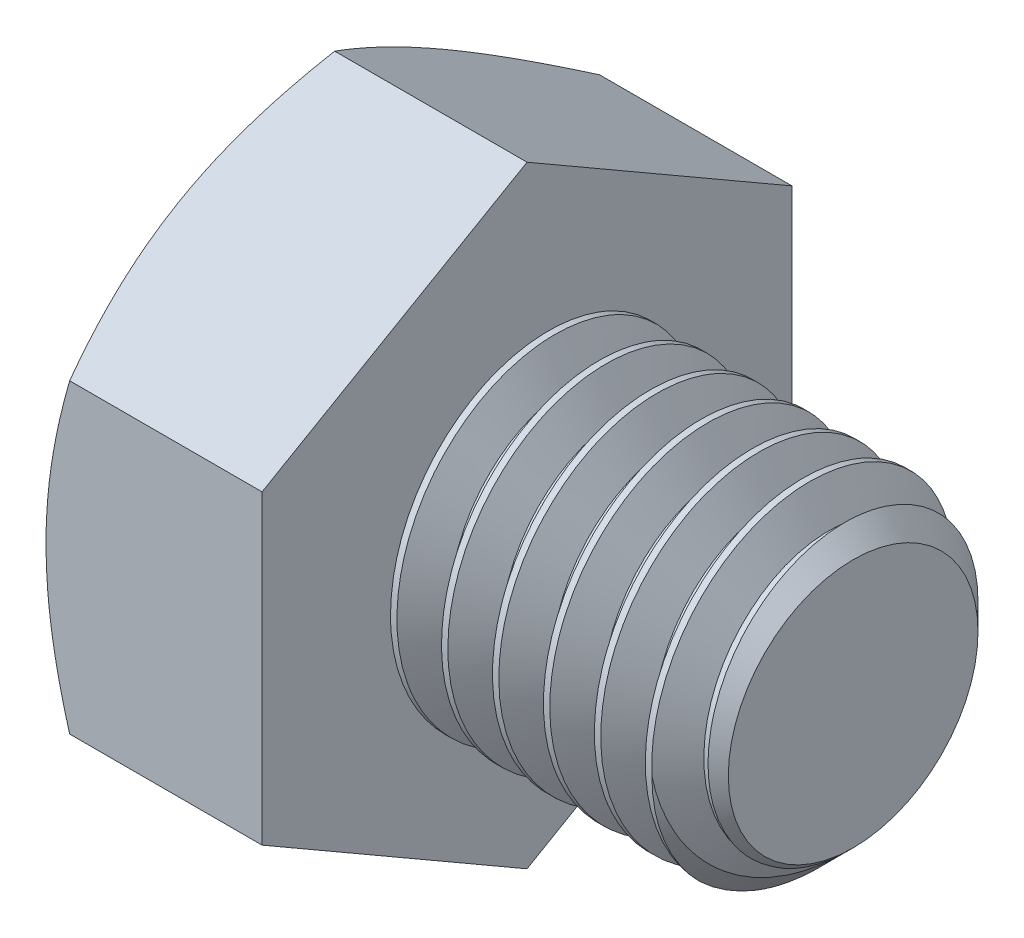
SolidWorks part; units mm, degrees
ref_plane "Front Plane" through (0, 0, 0) normal (0, 0, 1) x (1, 0, 0)
ref_plane "Top Plane" through (0, 0, 0) normal (0, 1, 0) x (1, 0, 0)
ref_plane "Right Plane" through (0, 0, 0) normal (1, 0, 0) x (0, 0, -1)
sketch "Sketch1" plane through (0, 0, 0) normal (0, 0, 1) x (1, 0, 0)
  line L0 (-6.65, 0) -> (6.65, 0) construction
  line L1 (-1.35, 6.5) -> (-1.35, -6.5) construction
  line L2 (-6.65, 6.5) -> (-6.65, -6.5) construction
  line L3 (6.65, 4) -> (6.65, -4) construction
  point P8 (2.275, -4)
  dimension "D1" = 4.375
  dimension "Thread Dia" = 8
  dimension "Hex" = 13
  dimension "Head Ht" = 5.3
  dimension "Length" = 8
ref_plane "Plane2" through (6.65, 0, 0) normal (1, 0, 0) x (0, 0, -1)
sketch "Sketch2" plane through (6.65, 0, 0) normal (1, 0, 0) x (0, 0, -1)
  circle A0 centre (0, 0) radius 4
extrude "Boss-Extrude1" add sketch "Sketch2" against normal up to vertex (8 mm away) up to point (-1.35, -6.5, 0)
sketch "Sketch4" plane through (6.65, 0, 0) normal (1, 0, 0) x (0, 0, -1)
  circle A1 centre (0, 0) radius 4
  circle A2 centre (0, 0) radius 4
  dimension "D1" = 0
curve "Helix/Spiral1" pitch 1.25 height 9.25 turns 7.4 parameters "Pitch"=1.25
chamfer "Chamfer1" distance 0.9375 angle 45 1 edges at (6.65, 0, -4)
sketch "Sketch5" plane through (0, 0, 0) normal (0, 0, 1) x (1, 0, 0)
  line L0 (6.65, 4) -> (7.1187, 3.1881)
  line L1 (7.1187, 3.1881) -> (7.275, 3.1881)
  line L2 (7.275, 3.1881) -> (7.7437, 4)
  line L3 (6.65, 4) -> (7.7437, 4)
  line L4 (7.1969, 3.1881) -> (7.1969, 4) construction
  line L5 (6.8844, 3.5941) -> (7.5094, 3.5941) construction
  line L6 (6.65, -4) -> (6.65, 4) construction
  dimension "D1" = 60
  dimension "D2" = 0.1562
  dimension "D3" = 0.625
sweep "Cut-Sweep1" cut profiles "Sketch5" path "Helix/Spiral1"
sketch "Sketch3" plane through (-1.35, 0, 0) normal (-1, 0, 0) x (0, 0, 1)
  line L0 (0, 6.5) -> (0, -6.5) construction
  line L1 (-6.5, -3.7528) -> (0, -7.5056)
  line L2 (0, -7.5056) -> (6.5, -3.7528)
  line L3 (6.5, -3.7528) -> (6.5, 3.7528)
  line L4 (6.5, 3.7528) -> (0, 7.5056)
  line L5 (0, 7.5056) -> (-6.5, 3.7528)
  line L6 (-6.5, 3.7528) -> (-6.5, -3.7528)
  circle A0 centre (0, 0) radius 6.5 construction
extrude "Boss-Extrude2" add sketch "Sketch3" along normal up to vertex (5.3 mm away) up to point (-6.65, -6.5, 0)
sketch "Sketch6" plane through (-6.65, 0, 0) normal (-1, 0, 0) x (0, 0, 1)
  circle A0 centre (0, 0) radius 6.5 construction
  circle A1 centre (0, 0) radius 6.5
extrude "Cut-Extrude1" cut sketch "Sketch6" against normal through all draft 60 flip side to cut
sketch "Sketch7" plane through (-6.65, 0, 0) normal (-1, 0, 0) x (0, 0, 1)
  line L0 (0, 0) -> (0, 6.5) construction
  line L2 (0, 6.5) -> (0, -6.5) construction
  line L3 (-5.6292, 3.25) -> (5.6292, 3.25) construction
  circle A1 centre (0, 0) radius 6.5 construction
  text T0 "8.8\r\n" font "Arial" height in points 6
  point P8 (0, 3.25)
extrude "Cut-Extrude2" cut sketch "Sketch7" against normal blind 0.25
sketch "Sketch9" plane through (0, 0, 0) normal (0, 0, 1) x (1, 0, 0)
  line L0 (-1.35, 4) -> (-1.35, 0)
  line L1 (-1.35, 0) -> (-43.35, 0)
  line L2 (-43.35, 0) -> (-47.35, 4)
  line L3 (-47.35, 4) -> (-1.35, 4)
  line L4 (-6.65, 0) -> (6.65, 0) construction
  line L5 (-1.35, 6.5) -> (-1.35, -6.5) construction
  line L6 (6.65, 4) -> (6.65, -4) construction
  dimension "D1" = 45
  dimension "MinThreadLg" = 54
revolve "Revolve1" [suppressed] add sketch "Sketch9" angle 360 about L1
equation "\"D2@Sketch5\" = \"Pitch@Helix/Spiral1\"*.125"
equation "\"D3@Sketch5\" = \"Pitch@Helix/Spiral1\"*.50"
equation "\"D3@Helix/Spiral1\" = \"Length@Sketch1\"+\"Pitch@Helix/Spiral1\""
equation "\"D1@Chamfer1\" = \"Pitch@Helix/Spiral1\"*.750"
equation "\"D1@Sketch1\" = \"Pitch@Helix/Spiral1\"*3.50"
